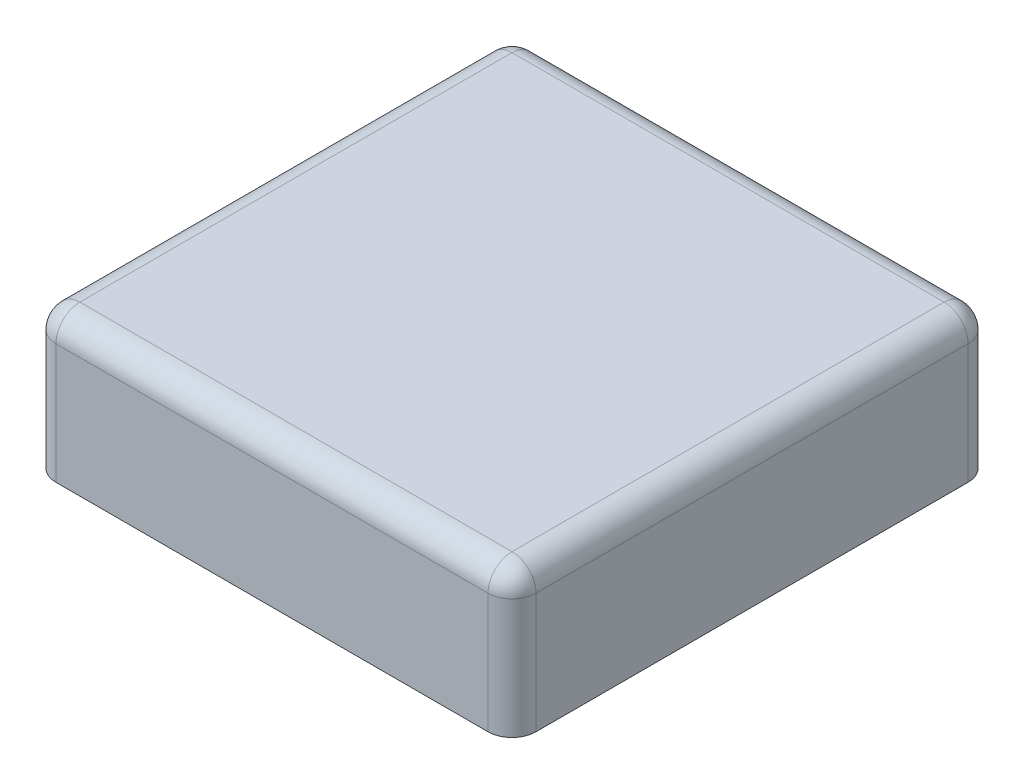
SolidWorks part; units mm, degrees
ref_plane "Front Plane" through (0, 0, 0) normal (0, 0, 1) x (1, 0, 0)
ref_plane "Top Plane" through (0, 0, 0) normal (0, 1, 0) x (1, 0, 0)
ref_plane "Right Plane" through (0, 0, 0) normal (1, 0, 0) x (0, 0, -1)
sketch "Sketch1" plane through (0, 0, 0) normal (0, 1, 0) x (1, 0, 0)
  line L1 (-5, 5) -> (5, 5)
  line L2 (-5, 5) -> (-5, -5)
  line L3 (-5, -5) -> (5, -5)
  line L4 (5, 5) -> (5, -5)
  line L5 (-5, 5) -> (5, -5) construction
  line L6 (-5, -5) -> (5, 5) construction
  point P0 (0, 0)
  dimension "D1" = 10
  dimension "D2" = 10
extrude "Boss-Extrude2" add sketch "Sketch1" against normal blind 3
shell "Shell2" thickness 0.7 removed face at (0, -3, 0)
fillet "Fillet2" radius 0.5 8 edges at (0, 0, 5) (-5, 0, 0) (0, 0, -5) (5, 0, 0) (-5, -1.5, -5) (5, -1.5, -5) (5, -1.5, 5) (-5, -1.5, 5)
sketch "Sketch5" plane through (0, 0, 0) normal (1, 0, 0) x (0, 0, -1)
  line L0 (3, -0.5) -> (3, -4.5)
  line L1 (4.5, -0.5) -> (-4.5, -0.5) construction
  line L2 (3, -4.5) -> (2.2, -4.5)
  line L3 (2.2, -4.5) -> (1.6836, -3.6056)
  line L4 (1.6836, -3.6056) -> (2.2, -2.7113)
  line L5 (2.2, -2.7113) -> (2.2, -0.5)
  line L6 (2.2, -0.5) -> (3, -0.5)
  line L7 (2.2, -2.7113) -> (2.2, -5.4101) construction
  line L8 (4.5, -3) -> (4.5, -0.5) construction
  line L9 (0, 0) -> (0, -5.7634) construction
  line L10 (-2.2, -2.7113) -> (-2.2, -5.4101) construction
  line L11 (-2.2, -0.5) -> (-3, -0.5)
  line L12 (-2.2, -2.7113) -> (-2.2, -0.5)
  line L13 (-1.6836, -3.6056) -> (-2.2, -2.7113)
  line L14 (-2.2, -4.5) -> (-1.6836, -3.6056)
  line L15 (-3, -4.5) -> (-2.2, -4.5)
  line L16 (-3, -0.5) -> (-3, -4.5)
  dimension "D1" = 150
  dimension "D2" = 150
  dimension "D3" = 0.8
  dimension "D4" = 1.5
  dimension "D5" = 4
extrude "Boss-Extrude3" add sketch "Sketch5" against normal mid plane 5 separate body
sketch "Sketch6" plane through (0, 0, 0) normal (0, 0, 1) x (1, 0, 0)
  line L0 (2.7, -0.5) -> (2.7, -4.3)
  line L1 (4.5, -0.5) -> (-4.5, -0.5) construction
  line L2 (2.7, -4.3) -> (1.9, -4.3)
  line L3 (1.9, -4.3) -> (1.9, -0.5)
  line L4 (1.9, -0.5) -> (2.7, -0.5)
  line L5 (4.5, -3) -> (4.5, -0.5) construction
  line L6 (0, 0) -> (0, -50000) construction
  line L7 (-1.9, -0.5) -> (-2.7, -0.5)
  line L8 (-1.9, -4.3) -> (-1.9, -0.5)
  line L9 (-2.7, -4.3) -> (-1.9, -4.3)
  line L10 (-2.7, -0.5) -> (-2.7, -4.3)
  dimension "D1" = 0.8
  dimension "D2" = 1.8
  dimension "D3" = 3.8
extrude "Boss-Extrude4" add sketch "Sketch6" along normal mid plane 2
sketch "Sketch7" plane through (0, 0, 0) normal (1, 0, 0) x (0, 0, -1)
  line L0 (-4.5, -0.5) -> (-3, -0.5)
  line L1 (4.5, -0.5) -> (-4.5, -0.5) construction
  line L2 (-3, -0.5) -> (-3, -4.5) construction
  line L3 (-3, -0.5) -> (-3, -2.7)
  line L4 (-3, -2.7) -> (-4.5, -2.7)
  line L5 (-4.5, -0.5) -> (-4.5, -3) construction
  line L6 (-4.5, -2.7) -> (-4.5, -0.5)
  line L7 (0, 0) -> (0, -50000) construction
  line L8 (4.5, -2.7) -> (4.5, -0.5)
  line L9 (3, -2.7) -> (4.5, -2.7)
  line L10 (3, -0.5) -> (3, -2.7)
  line L11 (4.5, -0.5) -> (3, -0.5)
  dimension "D1" = 2.2
extrude "Boss-Extrude5" add sketch "Sketch7" along normal mid plane 0.7
sketch "Sketch9" plane through (0, 0, 0) normal (0, 0, 1) x (1, 0, 0)
  line L0 (-4.5, -2.7) -> (-2.7, -2.7)
  line L1 (-4.5, -0.5) -> (-4.5, -3) construction
  line L2 (-2.7, -0.7) -> (-2.7, -4.3) construction
  line L3 (-2.7, -2.7) -> (-2.7, -0.5)
  line L4 (4.5, -0.5) -> (-4.5, -0.5) construction
  line L5 (-2.7, -0.5) -> (-4.5, -0.5)
  line L6 (-4.5, -0.5) -> (-4.5, -2.7)
  line L7 (0, -1000) -> (0, 49000) construction
  line L8 (4.5, -0.5) -> (4.5, -2.7)
  line L9 (2.7, -0.5) -> (4.5, -0.5)
  line L10 (2.7, -2.7) -> (2.7, -0.5)
  line L11 (4.5, -2.7) -> (2.7, -2.7)
  dimension "D1" = 2.2
extrude "Boss-Extrude6" add sketch "Sketch9" along normal mid plane 0.7
